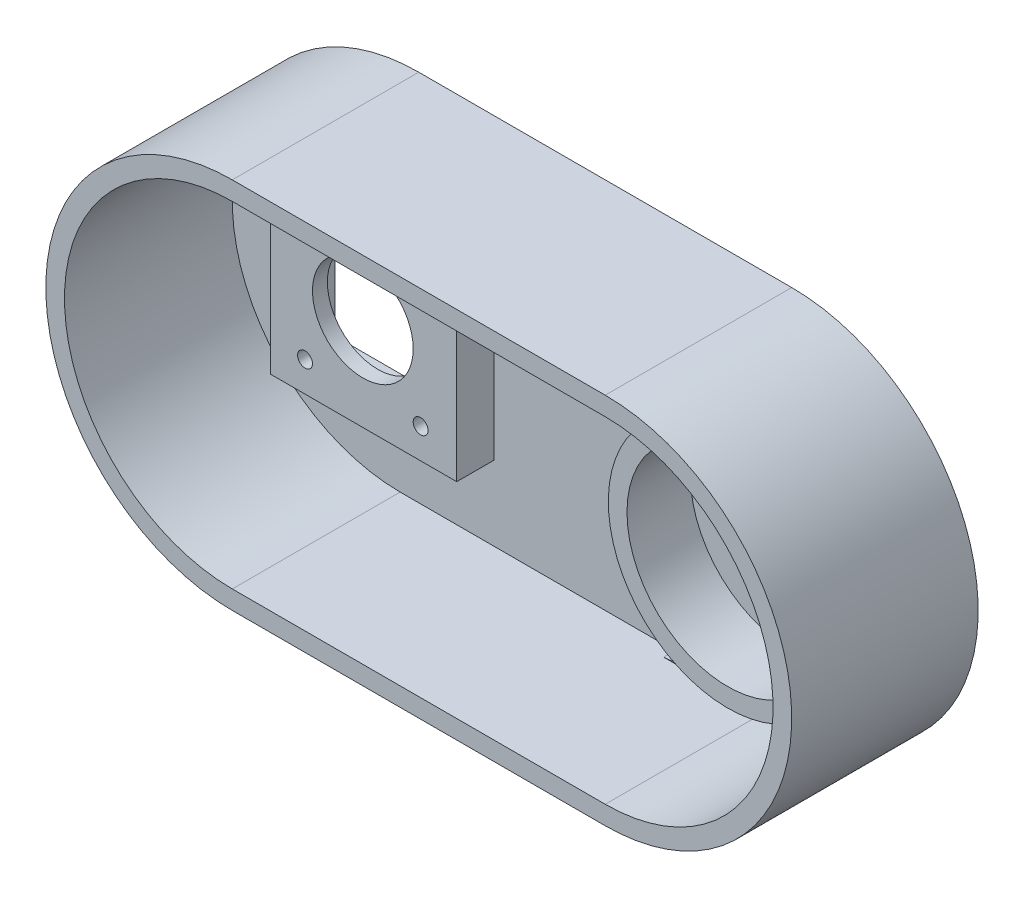
SolidWorks part; units mm, degrees
ref_plane "Front Plane" through (0, 0, 0) normal (0, 0, 1) x (1, 0, 0)
ref_plane "Top Plane" through (0, 0, 0) normal (0, 1, 0) x (1, 0, 0)
ref_plane "Right Plane" through (0, 0, 0) normal (1, 0, 0) x (0, 0, -1)
sketch "Sketch1" plane through (0, 0, 0) normal (0, 0, 1) x (1, 0, 0)
  line L0 (46.31, 0) -> (-53.69, 0) construction
  line L1 (46.31, -45) -> (-53.69, -45)
  line L2 (46.31, 45) -> (-53.69, 45)
  arc A0 (46.31, -45) -> (46.31, 45) centre (46.31, 0) ccw
  arc A1 (-53.69, 45) -> (-53.69, -45) centre (-53.69, 0) ccw
  point P3 (-3.69, 0)
  point P8 (-53.69, 0)
  dimension "D1" = 45
extrude "Extrude-Thin1" add sketch "Sketch1" along normal blind 50 thin contours L2 A1 L1 A0 thin type one direction wall 5
extrude "Boss-Extrude1" add sketch "Sketch1<3>" along normal blind 5 contours L2 A1 L1 A0 region at (-3.69, 0, 0)
sketch "Sketch1<3>" plane through (0, 0, 0) normal (0, 0, 1) x (1, 0, 0) same geometry as "Sketch1"
sketch "Sketch2" plane through (0, 0, 0) normal (0, 0, -1) x (-1, 0, 0)
  circle A0 centre (-51.1407, -2.2577) radius 12.5
  dimension "D1" = 25
sketch "Sketch4" plane through (0, 0, 5) normal (0, 0, 1) x (1, 0, 0)
  circle A0 centre (51.1407, -2.2577) radius 26.5
  dimension "D1" = 53
sketch "Sketch5" plane through (0, 0, 5) normal (0, 0, 1) x (1, 0, 0)
  circle A0 centre (51.1407, -2.2577) radius 32
  dimension "D1" = 64
extrude "Extrude-Thin4" add sketch "Sketch5" along normal blind 17 thin thin type one direction reverse wall 5
extrude "Cut-Extrude2" cut sketch "Sketch2" against normal through all contours A0
sketch "Sketch10" plane through (0, 0, 5) normal (0, 0, 1) x (1, 0, 0)
  line L0 (51.1407, 29.7423) -> (46.31, 45)
  line L1 (46.31, 45) -> (33.0788, 45)
  line L2 (46.31, 45) -> (-53.69, 45) construction
  line L3 (33.0788, 45) -> (40.9577, 28.0788)
  line L4 (51.1407, 29.7423) -> (41.321, 28.1984)
  line L5 (41.321, 28.1984) -> (40.9577, 28.0788)
  circle A0 centre (51.1407, -2.2577) radius 32 construction
extrude "Boss-Extrude4" add sketch "Sketch10" along normal blind 3
fillet "Fillet1" radius 10 1 edges
fillet "Fillet2" radius 10 1 edges at (51.1407, 29.7423, 6.5)
sketch "Sketch11" plane through (0, 0, 5) normal (0, 0, 1) x (1, 0, 0)
  line L0 (34.7565, -29.7452) -> (25.6637, -45)
  line L1 (46.31, -45) -> (-53.69, -45) construction
  line L2 (25.6637, -45) -> (38.4867, -45)
  line L3 (38.4867, -45) -> (41.405, -32.7408)
  line L4 (41.405, -32.7408) -> (34.7565, -29.7452)
  circle A0 centre (51.1407, -2.2577) radius 32 construction
extrude "Boss-Extrude5" add sketch "Sketch11" along normal blind 3
fillet "Fillet3" radius 10 1 edges at (38.4867, -45, 6.5)
fillet "Fillet4" radius 10 1 edges at (25.6637, -45, 6.5)
sketch "Sketch13" plane through (0, 0, 5) normal (0, 0, 1) x (1, 0, 0)
  line L0 (90.7057, -8.7247) -> (82.5015, -8.7247)
  line L1 (82.5015, -8.7247) -> (83.0847, 0)
  line L2 (83.0847, 0) -> (91.6675, 0)
  line L3 (91.6675, 0) -> (90.7057, -8.7247)
extrude "Boss-Extrude11" add sketch "Sketch13" along normal blind 3
fillet "Fillet6" radius 10 1 edges at (91.31, 0, 6.5)
fillet "Fillet7" radius 10 1 edges at (90.4561, -8.7247, 6.5)
sketch "Sketch14" plane through (0, 0, 5) normal (0, 0, 1) x (1, 0, 0)
  line L1 (-78.5075, -25) -> (-28.5075, -25)
  line L2 (-78.5075, -25) -> (-78.5075, 25)
  line L3 (-78.5075, 25) -> (-28.5075, 25)
  line L4 (-28.5075, -25) -> (-28.5075, 25)
  line L5 (-78.5075, -25) -> (-28.5075, 25) construction
  line L6 (-78.5075, 25) -> (-28.5075, -25) construction
  point P0 (-53.5075, 0)
  dimension "D1" = 50
  dimension "D2" = 50
extrude "Boss-Extrude12" add sketch "Sketch14" along normal blind 10
sketch "Sketch16" plane through (0, 0, 15) normal (0, 0, 1) x (1, 0, 0)
  line L0 (-53.69, 22.5) -> (-53.69, -22.5) construction
  line L1 (-76.19, -22.5) -> (-31.19, -22.5)
  line L2 (-76.19, -22.5) -> (-76.19, 22.5)
  line L3 (-76.19, 22.5) -> (-31.19, 22.5)
  line L4 (-31.19, -22.5) -> (-31.19, 22.5)
  line L5 (-76.19, -22.5) -> (-31.19, 22.5) construction
  line L6 (-76.19, 22.5) -> (-31.19, -22.5) construction
  circle A0 centre (-53.69, 0) radius 13.5
  circle A1 centre (-69.19, 14.0434) radius 2
  circle A4 centre (-69.19, -16.9566) radius 2
  circle A5 centre (-38.19, -16.9566) radius 2
  circle A6 centre (-38.19, 14.0434) radius 2
  point P0 (-53.69, 0)
  dimension "D3" = 27
  dimension "D4" = 4
  dimension "D1" = 45
  dimension "D2" = 45
  dimension "D5" = 31
  dimension "D6" = 31
extrude "Cut-Extrude5" cut sketch "Sketch16" against normal blind 25 from offset 4 offset against normal yes
extrude "Cut-Extrude6" cut sketch "Sketch16<2>" against normal through all contours A6 | A1 | A0 | A4 | A5 region at (-53.69, 0, 15) region at (-69.19, 14.0434, 15) region at (-69.19, -16.9566, 15) region at (-38.19, 14.0434, 15)
sketch "Sketch16<2>" plane through (0, 0, 15) normal (0, 0, 1) x (1, 0, 0) same geometry as "Sketch16"
